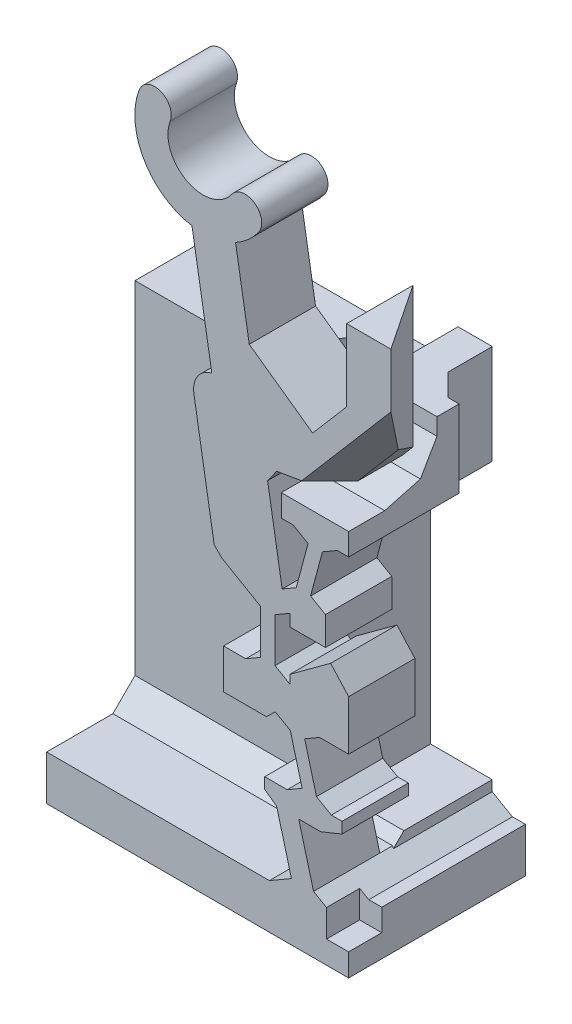
SolidWorks part; units mm, degrees
material "Nylon 6/12"
ref_plane "Front Plane" through (0, 0, 0) normal (0, 0, 1) x (1, 0, 0)
ref_plane "Top Plane" through (0, 0, 0) normal (0, 1, 0) x (1, 0, 0)
ref_plane "Right Plane" through (0, 0, 0) normal (1, 0, 0) x (0, 0, -1)
sketch "Sketch-SkeletonConfigUp" plane through (0, 0, 0) normal (0, 0, 1) x (1, 0, 0)
  line L0 (0, 0) -> (0, -50000) construction
  line L1 (0, 0) -> (4.5811, 6.2164) construction
  line L2 (9.8143, 13.3177) -> (4.5811, 13.945) construction
  line L3 (4.5811, 13.945) -> (2.9713, 10.4094) construction
  line L4 (2.9713, 10.4094) -> (4.5811, 6.2164) construction
  line L5 (4.5811, 13.945) -> (6.2429, 19.1409) construction
  line L6 (2.9713, 10.4094) -> (0.0405, 27.8193) construction
  line L7 (4.5811, 6.2164) -> (9.8143, 13.3177) construction
  line L8 (-587.3593, -797.0242) -> (9.8143, 13.3177) construction
  dimension "D2" = 7.7221
  dimension "D3" = 8.8212
  dimension "D4" = 5.2707
  dimension "D5" = 119.553
  dimension "D6" = 3.8848
  dimension "D7" = 5.4552
  dimension "D8" = 17.6549
  dimension "D9" = 4.4914
  dimension "D10" = 6.745
  dimension "D11" = 145.964
  dimension "D12" = 143.612
sketch "Sketch-SkeletonConfigDown" plane through (0, 0, 0) normal (0, 0, 1) x (1, 0, 0)
  line L0 (0, 0) -> (0, -50000) construction
  line L1 (0, 0) -> (4.5811, 6.2164) construction
  line L2 (9.8143, 13.3177) -> (4.5811, 13.945) construction
  line L3 (4.5811, 13.945) -> (6.1909, 10.4094) construction
  line L4 (6.1909, 10.4094) -> (4.5811, 6.2164) construction
  line L5 (4.5811, 13.945) -> (1.753, 18.6098) construction
  line L6 (6.1909, 10.4094) -> (-8.8652, 19.6294) construction
  line L7 (4.5811, 6.2164) -> (9.8143, 13.3177) construction
  line L8 (-589.9357, -800.5203) -> (9.8143, 13.3177) construction
  dimension "D2" = 7.7221
  dimension "D3" = 8.8212
  dimension "D4" = 5.2707
  dimension "D5" = 119.553
  dimension "D6" = 3.8848
  dimension "D7" = 5.4552
  dimension "D8" = 17.6549
  dimension "D9" = 4.4914
  dimension "D10" = 6.745
  dimension "D11" = 145.964
  dimension "D1" = 143.612
ref_plane "Plane-Cam Base" through (9.128, 0, 0) normal (1, 0, 0) x (0, 0, -1)
ref_plane "Plane-Down-to-Up Derailleur Clearance" through (6.628, 0, 0) normal (1, 0, 0) x (0, 0, -1)
ref_plane "Plane-Cam Cavity Roof" through (5.128, 0, 0) normal (1, 0, 0) x (0, 0, -1)
sketch "Sketch-SwitchBossUp" plane through (0, 0, 0) normal (0, 0, 1) x (1, 0, 0)
  line L0 (3.5811, 11.4759) -> (3.5811, 12.945) construction
  line L2 (6.5405, 21.1774) -> (6.5405, 24.4384)
  line L3 (6.5405, 24.4384) -> (8.5405, 24.4384)
  line L4 (8.5405, 24.4384) -> (8.5405, 20.4384)
  line L5 (5.5811, 12.5552) -> (5.5811, 11.263)
  line L7 (1.5115, 25.1048) -> (2.5464, 18.9575)
  line L8 (-0.4607, 24.7728) -> (0.4359, 19.4465)
  line L9 (2.9713, 10.4094) -> (0.0405, 27.8193) construction
  line L11 (-0.0396, 22.2712) -> (1.9326, 22.6032) construction
  line L15 (6.628, -55) -> (6.628, 55) construction
  line L16 (2.9713, 10.4094) -> (4.5811, 6.2164) construction
  line L17 (3.5811, 12.945) -> (3.5811, 14.945) construction
  line L18 (5.5811, 12.945) -> (5.5811, 14.945) construction
  line L19 (4.2561, 13.945) -> (4.9061, 13.945) construction
  line L20 (3.5811, 14.945) -> (5.5811, 14.945) construction
  line L21 (3.5811, 12.945) -> (5.5811, 12.945) construction
  line L22 (4.5811, 12.945) -> (4.5811, 14.945) construction
  line L23 (4.5811, 6.2164) -> (8.5405, 7.1023) construction
  line L24 (1.9713, 9.4094) -> (1.9713, 11.4094) construction
  line L25 (3.9713, 9.4094) -> (3.9713, 11.4094) construction
  line L26 (3.9713, 9.4094) -> (1.9713, 9.4094) construction
  line L27 (1.9713, 11.4094) -> (3.9713, 11.4094) construction
  line L28 (3.5811, 7.2164) -> (5.5811, 7.2164) construction
  line L29 (3.5811, 7.2164) -> (3.5811, 5.2164) construction
  line L30 (5.5811, 7.2164) -> (5.5811, 5.2164) construction
  line L31 (3.5811, 5.2164) -> (5.5811, 5.2164) construction
  line L32 (4.9061, 6.2164) -> (4.2561, 6.2164) construction
  line L40 (3.2963, 10.4094) -> (2.6463, 10.4094) construction
  line L43 (2.874, 4.5093) -> (0.7934, 4.5093) construction
  line L51 (4.9929, 19.3693) -> (2.5464, 18.9575)
  line L66 (0.0405, 27.8193) -> (0.0405, 50027.8193) construction
  line L74 (0.5455, 12.7717) -> (-0.3728, 18.2264)
  line L75 (0.3841, 13.7302) -> (2.3564, 14.0622) construction
  line L76 (5.5811, 11.263) -> (5.5811, 12.5552) construction
  line L80 (5.8152, 10.763) -> (6.628, 9.8603)
  line L81 (8.5405, 1033.6218) -> (8.5405, 20.4384) construction
  line L82 (2.5464, 18.9575) -> (3.5585, 12.945) construction
  line L83 (3.6203, 12.5779) -> (2.8784, 16.9852)
  line L84 (2.8784, 16.9852) -> (6.0405, 17.5175)
  line L85 (6.9307, 9.5241) -> (8.5405, 7.7363) construction
  line L88 (3.5811, 16.3347) -> (6.8573, 16.3347)
  line L92 (3.7762, 8.3129) -> (6.9307, 9.5241) construction
  line L93 (6.3311, 4.3289) -> (5.3706, 3.937)
  line L95 (2.5464, 18.9575) -> (2.8784, 16.9852) construction
  line L96 (2.7124, 17.9713) -> (8.5405, 18.9524) construction
  line L97 (2.7124, 17.9713) -> (1.7262, 17.8053) construction
  line L98 (1.9713, 9.0197) -> (0.9713, 9.0197)
  line L99 (0.9713, 9.0197) -> (0.9713, 7.2164)
  line L100 (0.9713, 7.2164) -> (2.9061, 7.2164)
  line L101 (4.5811, 6.2164) -> (6.9307, 9.5241) construction
  line L103 (0.0405, 27.8193) -> (1.9448, 26.4638) construction
  line L104 (6.9307, 9.5241) -> (8.5405, 7.7363) construction
  line L106 (13.4416, 14.945) -> (5.5811, 14.945) construction
  line L107 (1.9713, 9.4094) -> (1.9713, 9.0197) construction
  line L109 (0.0405, 27.8193) -> (-2.1498, 28.6358) construction
  line L110 (8.5405, 20.4384) -> (6.0405, 17.5175)
  line L111 (6.628, 9.8603) -> (6.628, 8.3653)
  line L112 (6.628, 9.8603) -> (6.9307, 9.5241) construction
  line L113 (2.8311, 4.8267) -> (2.8311, 4.3267)
  line L114 (7.3693, 7.7363) -> (7.3563, 7.7363) construction
  line L115 (6.8573, 16.3347) -> (13.4416, 16.3347)
  line L116 (13.4416, 16.3347) -> (13.4416, -1.1653)
  line L117 (13.4416, -1.1653) -> (5.0405, -1.1653)
  line L119 (10.4375, 14.0252) -> (10.4375, 2.1692)
  line L121 (5.0405, -1.1653) -> (5.0405, 1.437) construction
  line L122 (8.237, 12.8031) -> (10.8393, 12.8031) construction
  line L123 (10.8393, 12.8031) -> (13.4416, 12.8031) construction
  line L124 (10.4375, 2.1692) -> (9.128, 0.8597)
  line L125 (8.5405, 7.5847) -> (13.4416, 7.5847) construction
  line L127 (5.5811, 15.3347) -> (5.5811, 14.945) construction
  line L130 (6.0405, 0.8597) -> (9.128, 0.8597)
  line L132 (2.8311, 4.3267) -> (3.3706, 3.937)
  line L133 (2.9713, 10.4094) -> (6.1909, 10.4094) construction
  line L134 (4.5811, 10.4094) -> (4.5811, 13.945) construction
  line L135 (4.5811, 10.4094) -> (4.5811, 6.2164) construction
  line L136 (0.8973, 12.4192) -> (0.5455, 12.7717)
  line L137 (3.9713, 9.4094) -> (5.5811, 7.2164) construction
  line L139 (5.8152, 10.763) -> (3.9713, 9.4094)
  line L141 (4.0405, 1.437) -> (3.0405, 0.8597)
  line L142 (3.0405, 0.8597) -> (3.0405, -1.1653)
  line L143 (8.5405, 20.4384) -> (8.5405, 18.9524) construction
  line L145 (8.5405, 17.9384) -> (8.5405, -49992.0368) construction
  line L147 (5.5811, 11.263) -> (5.5811, 12.5552) construction
  line L149 (6.3311, 4.8289) -> (6.3311, 4.3289)
  line L150 (3.0405, -1.1653) -> (5.0405, -1.1653)
  line L151 (3.3706, 3.937) -> (5.3706, 3.937) construction
  line L152 (4.792, 14.945) -> (4.2561, 12.945)
  line L153 (5.442, 14.945) -> (4.9061, 12.945)
  line L157 (3.5811, 16.3347) -> (3.5811, 15.3347)
  line L158 (6.117, 15.3347) -> (9.128, 15.3347)
  line L162 (3.2963, 11.4094) -> (3.2963, 9.4094)
  line L164 (2.6463, 11.4094) -> (2.6463, 9.4094)
  line L169 (3.9882, 7.2164) -> (4.5241, 5.2164)
  line L170 (5.1741, 5.2164) -> (4.6382, 7.2164)
  line L176 (4.6382, 7.2164) -> (5.315, 7.6072)
  line L177 (5.5811, 7.2164) -> (5.5811, 7.6072) construction
  line L180 (3.5811, 5.2164) -> (3.5811, 4.8267) construction
  line L181 (3.5811, 4.8267) -> (2.8311, 4.8267)
  line L184 (5.5811, 5.2164) -> (5.5811, 4.8267) construction
  line L186 (9.128, -55) -> (9.128, 55) construction
  line L187 (2.6463, 9.4094) -> (1.9713, 9.0197)
  line L188 (3.2963, 9.4094) -> (3.9713, 9.0197)
  line L189 (3.2963, 11.4094) -> (3.9713, 11.7991)
  line L190 (2.6463, 11.4094) -> (0.8973, 12.4192)
  line L191 (3.9713, 11.4094) -> (3.9713, 11.7991) construction
  line L192 (3.9713, 11.7991) -> (3.9713, 11.263)
  line L193 (4.9061, 12.945) -> (5.5811, 12.5552)
  line L194 (4.2561, 12.945) -> (3.6203, 12.5779)
  line L195 (3.9713, 11.263) -> (5.5811, 11.263)
  line L196 (3.9713, 9.4094) -> (3.9713, 9.0197)
  line L197 (3.5811, 7.2164) -> (3.5811, 7.6072) construction
  line L200 (5.8453, 4.8289) -> (6.3311, 4.8289)
  line L201 (2.8311, 4.3267) -> (2.8311, 3.937) construction
  line L202 (2.8311, 3.937) -> (3.3706, 3.937) construction
  line L203 (10.4375, 14.0252) -> (9.128, 15.3347)
  line L204 (5.0405, 1.437) -> (3.0405, 1.437) construction
  line L205 (3.0405, 1.437) -> (3.0405, 0.8597) construction
  line L206 (5.0405, 1.437) -> (6.0405, 0.8597)
  line L207 (8.5405, 18.9524) -> (8.5405, 17.9384) construction
  line L208 (6.0405, 17.5175) -> (8.5405, 17.9384) construction
  line L209 (8.5405, 20.4384) -> (8.5405, 17.9384) construction
  line L210 (6.5405, 21.1774) -> (4.9929, 19.3693)
  line L211 (5.0405, 1.437) -> (4.3706, 3.937)
  line L212 (4.0405, 1.437) -> (3.3706, 3.937)
  line L213 (5.3706, 3.937) -> (4.3706, 3.937)
  line L214 (4.792, 14.945) -> (4.1169, 15.3347)
  line L215 (4.1169, 15.3347) -> (3.5811, 15.3347)
  line L216 (5.442, 14.945) -> (6.117, 15.3347)
  line L217 (5.5811, 12.945) -> (5.5811, 12.5552) construction
  line L218 (5.442, 14.945) -> (5.442, 15.3347) construction
  line L219 (6.117, 15.3347) -> (4.1169, 15.3347) construction
  line L220 (3.5811, 4.8267) -> (5.5811, 4.8267) construction
  line L221 (4.5241, 5.2164) -> (3.8491, 4.8267)
  line L222 (3.8491, 4.8267) -> (3.5811, 4.8267)
  line L223 (5.1741, 5.2164) -> (5.8453, 4.8289)
  line L224 (3.5811, 7.6072) -> (5.5811, 7.6072) construction
  line L225 (3.9882, 7.2164) -> (3.3114, 7.6072)
  line L226 (5.315, 7.6072) -> (6.628, 7.6072)
  line L227 (6.628, 7.6072) -> (6.628, 8.3653)
  line L228 (3.5811, 7.6072) -> (0.9713, 7.6072) construction
  line L229 (3.3114, 7.6072) -> (2.9061, 7.2164)
  arc A0 (1.5115, 25.1048) -> (2.5558, 26.0289) centre (0.0405, 27.8193) ccw
  arc A1 (-0.4607, 24.7728) -> (-2.8525, 28.8978) centre (0.0405, 27.8193) cw
  arc A2 (-2.8525, 28.8978) -> (-1.447, 28.3738) centre (-2.1498, 28.6358) cw
  arc A3 (2.5558, 26.0289) -> (1.3338, 26.8987) centre (1.9448, 26.4638) ccw
  arc A4 (-1.447, 28.3738) -> (1.3338, 26.8987) centre (0.0405, 27.8193) ccw
  arc A5 (3.5811, 12.945) -> (3.5811, 14.945) centre (3.1778, 13.945) ccw construction
  arc A6 (5.5811, 12.945) -> (5.5811, 14.945) centre (5.9843, 13.945) cw construction
  arc A7 (2.5293, 9.921) -> (1.9713, 11.4094) centre (1.568, 10.4094) ccw construction
  arc A8 (3.9713, 11.4094) -> (3.9713, 9.4094) centre (4.3745, 10.4094) ccw construction
  arc A9 (3.5811, 7.2164) -> (3.5811, 5.2164) centre (3.1779, 6.2164) cw construction
  arc A10 (5.5811, 7.2164) -> (5.5811, 5.2164) centre (5.9844, 6.2164) ccw construction
  arc A19 (-0.3728, 18.2264) -> (0.4359, 19.4465) centre (0.6836, 18.4042) cw
  circle A28 centre (0.0405, 27.8193) radius 2.3375 construction
  arc A29 (1.9713, 9.4094) -> (2.5293, 9.921) centre (1.568, 10.4094) ccw construction
  point P53 (4.5811, 13.945)
  point P63 (2.9713, 10.4094)
  point P93 (0.9465, 22.4372)
  dimension "D23" = 1.5875
  dimension "D24" = 0.75
  dimension "D2" = 2
  dimension "D5" = 2
  dimension "D6" = 0.65
  dimension "D8" = 42
  dimension "D7" = 2
  dimension "D11" = 8.5
  dimension "D14" = 7.5
  dimension "D4" = 3
  dimension "D16" = 42
  dimension "D31" = 120
  dimension "D32" = 120
  dimension "D33" = 120
  dimension "D34" = 120
  dimension "D17" = 0.5
  dimension "D20" = 3.5
  dimension "D21" = 1
  dimension "D18" = 45
  dimension "D9" = 17.5
  dimension "D22" = 1
  dimension "D15" = 45
  dimension "D38" = 2
  dimension "D39" = 0.5
  dimension "D41" = 1
  dimension "D42" = 45
  dimension "D43" = 120
  dimension "D44" = 2
  dimension "D45" = 2.5
  dimension "D46" = 2.5
  dimension "D47" = 4
  dimension "D48" = 2
  dimension "D10" = 15
  dimension "D12" = 2.5
  dimension "D13" = 1
  dimension "D19" = 1
  dimension "D25" = 15
  dimension "D26" = 120
  dimension "D35" = 120
  dimension "D27" = 15
  dimension "D28" = 30
  dimension "D29" = 30
  dimension "D30" = 30
  dimension "D36" = 30
extrude "Boss-Switch Body" add sketch "Sketch-SwitchBossUp" along normal blind 3
sketch "Sketch1" plane through (0, 0, 0) normal (0, 0, -1) x (-1, 0, 0)
  line L1 (-7.5811, -1.1653) -> (0.4122, -1.1653)
  line L2 (-7.5811, -1.1653) -> (-7.5811, 0.8597)
  line L4 (0.4122, -1.1653) -> (0.4122, 0.8597)
  line L5 (-3.5811, 18.8347) -> (-7.5811, 18.8347)
  line L10 (-7.5811, 18.8347) -> (-7.5811, 15.3347)
  line L11 (-4.0405, 1.437) -> (-5.0405, 1.437)
  line L12 (-7.5811, 15.3347) -> (-3.5811, 15.3347)
  line L13 (-4.0405, 1.437) -> (-3.0405, 0.8597)
  line L14 (-3.5811, 15.3347) -> (-3.5811, 18.8347)
  line L20 (-4.3706, 3.937) -> (-5.0405, 1.437) construction
  line L22 (-3.0405, -1.1653) -> (-13.4416, -1.1653) construction
  line L23 (-3.0405, 0.8597) -> (0.4122, 0.8597)
  line L24 (-5.0405, 1.437) -> (-6.0405, 0.8597)
  line L25 (-6.0405, 0.8597) -> (-7.5811, 0.8597)
  line L27 (-3.5811, 16.3347) -> (-3.5811, 15.3347) construction
  point P5 (-3.5811, 15.3347)
  dimension "D1" = 3.5
  dimension "D4" = 4
extrude "Boss-Flange Width" add sketch "Sketch1" along normal blind 5
ref_plane "Plane-Sta2Sit Groove" through (0.0405, 0, 0) normal (1, 0, 0) x (0, 0, -1)
ref_plane "Plane-Cam Outer Surface" through (-12.0395, 0, 0) normal (1, 0, 0) x (0, 0, -1)
ref_plane "Plane-FlangeTop" through (-7.0395, 0, 0) normal (1, 0, 0) x (0, 0, -1)
sketch "Sketch2" plane through (-7.0395, 0, 0) normal (1, 0, 0) x (0, 0, -1)
  line L0 (5, 15.3347) -> (-3, 15.3347) construction
  line L1 (5, 17.3347) -> (1, 17.3347)
  line L2 (5, 17.3347) -> (5, 15.3347)
  line L3 (5, 15.3347) -> (1, 15.3347)
  line L4 (1, 17.3347) -> (1, 15.3347)
  line L10 (-3, -1.1653) -> (-3, 16.3347) construction
  line L11 (5, 0.8597) -> (-3, 0.8597)
  line L12 (5, 0.8597) -> (5, -1.1653)
  line L13 (5, -1.1653) -> (-3, -1.1653)
  line L14 (-3, 0.8597) -> (-3, -1.1653)
  line L15 (0, 10.4094) -> (0, 27.8193) construction
  line L17 (5, 0.8597) -> (5, -1.1653) construction
  line L18 (-3, 0.8597) -> (0, 0.8597) construction
  dimension "D1" = 1
  dimension "D2" = 2
extrude "Boss-Flange Height" add sketch "Sketch2" along normal up to surface (11.6675 mm away)
sketch "Sketch10" plane through (0, 15.3347, 0) normal (0, 1, 0) x (1, 0, 0)
  line L0 (9.128, -55) -> (9.128, 55) construction
  line L1 (7.5811, 5) -> (5.128, 5)
  line L2 (7.5811, 5) -> (7.5811, 2)
  line L3 (7.5811, 2) -> (5.128, 2)
  line L5 (4.628, 7) -> (4.628, 1) construction
  line L6 (3.5811, 1) -> (-7.0395, 1) construction
  line L8 (5.128, 5) -> (5.128, 2)
  dimension "D1" = 1
  dimension "D2" = 0.5
  dimension "D3" = 4.5
extrude "Cut-Up-To-Down Derailleur Clearance" cut sketch "Sketch10" along normal up to next
sketch "Sketch17" plane through (0, 15.3347, 0) normal (0, -1, 0) x (1, 0, 0)
  line L0 (5.128, -5) -> (-7.0395, -5)
  line L1 (5.128, -5) -> (-7.0395, -5) construction
  line L2 (-7.0395, -5) -> (-7.0395, -1)
  line L3 (-7.0395, -1) -> (5.128, -1)
  line L4 (5.128, -1) -> (5.128, -5)
  line L5 (-7.0395, -1) -> (-7.0395, -5) construction
extrude "Boss-Flange Support" add sketch "Sketch17" along normal up to surface (14.475 mm away) up to face at (-1.9995, 0.8597, -1)
sketch "Sketch-HolePositions" plane through (0, -1.1653, 0) normal (0, -1, 0) x (1, 0, 0)
  line L0 (-7.0395, -3) -> (7.5811, -3) construction
  line L1 (7.5811, -5) -> (-7.0395, -5) construction
  line L2 (7.5811, -5) -> (7.5811, 0) construction
  line L4 (-7.0395, -22.2167) -> (-7.0395, 22.2167) construction
  line L5 (3.5811, -1) -> (3.5811, -5) construction
  point P6 (-4.0395, -3)
  point P7 (0.5811, -3)
  dimension "D1" = 3
  dimension "D2" = 3
  dimension "D3" = 2
sketch "Sketch6" plane through (0, -1.1653, 0) normal (0, -1, 0) x (-1, 0, 0)
  point P0 (4.0395, 3)
  point P3 (-0.5811, 3)
hole_wizard "Tap Drill for M2x0.4 Tap1" positions "Sketch6" profile "Sketch5" hole size "M2x0.4" standard "ANSI Metric" end condition through all
sketch "Sketch5" plane through (-4.0395, -1.1653, -3) normal (1, 0, 0) x (0, 0, -1)
  line L0 (0, 0) -> (0, 30.5511)
  line L1 (0, 30.5511) -> (0.8, 30.5511)
  line L2 (0.8, 30.5511) -> (0.8, 0)
  line L5 (0.8, 0) -> (0, 0)
  line L11 (0, -6.35) -> (0, 107.95) construction
  dimension "Thru Hole Dia." = 1.6
  dimension "Thru Hole Depth" = 30.5511
sketch "Sketch9" plane through (0, -1.1653, 0) normal (0, -1, 0) x (1, 0, 0)
  point P0 (-4.0395, -3)
  point P3 (0.5811, -3)
hole_wizard "M2 Clearance Hole2" positions "Sketch9" profile "Sketch8" hole size "M2" standard "ANSI Metric"
sketch "Sketch8" plane through (-4.0395, -1.1653, -3) normal (1, 0, 0) x (0, 0, -1)
  line L0 (0, 0) -> (0, 15.721)
  line L1 (0, 15.721) -> (1.2, 15)
  line L2 (1.2, 15) -> (1.2, 0)
  line L5 (1.2, 0) -> (0, 0)
  line L10 (0, 15.721) -> (-1.2, 15) construction
  line L11 (0, -6.35) -> (0, 107.95) construction
  dimension "Hole Dia." = 2.4
  dimension "Hole Depth" = 15
  dimension "Drill Angle" = 118
sketch "Sketch-Measurements for Derailleur Ramps" plane through (0, 0, 0) normal (0, 0, 1) x (1, 0, 0)
  line L0 (2.8784, 16.9852) -> (2.5464, 18.9575)
  line L1 (2.7124, 17.9713) -> (1.7262, 17.8053)
  line L2 (2.9713, 10.4094) -> (0.0405, 27.8193) construction
  line L3 (1.7262, 17.8053) -> (-1.8937, 15.3603)
  line L4 (6.1909, 10.4094) -> (-8.8652, 19.6294) construction
  line L5 (1.7262, 17.8053) -> (2.6012, 12.6077)
  line L6 (2.6012, 12.6077) -> (-1.8937, 15.3603)
  line L7 (-0.0837, 16.5828) -> (-0.0837, 17.8053)
  line L8 (-0.0837, 17.8053) -> (1.7262, 17.8053)
  line L9 (6.1909, 10.4094) -> (2.9713, 10.4094)
  line L10 (5.386, 8.3129) -> (3.7762, 8.3129)
  line L12 (6.1909, 10.4094) -> (4.5811, 6.2164) construction
  line L13 (4.5811, 8.3129) -> (4.5811, 8.7912)
  line L14 (4.5811, 6.2164) -> (5.386, 8.3129)
  line L15 (2.9713, 10.4094) -> (4.5811, 6.2164) construction
  line L16 (3.7762, 8.3129) -> (4.5811, 6.2164)
  line L17 (5.386, 8.3129) -> (5.386, 8.7912)
  dimension "D1" = 1.81
  dimension "D2" = 0.8049
sketch "Sketch12" plane through (0, 24.4384, 0) normal (0, 1, 0) x (1, 0, 0)
  line L0 (6.5405, 0) -> (8.5405, -3)
  line L1 (8.5405, -3) -> (8.5405, 0)
  line L2 (8.5405, 0) -> (6.5405, 0)
extrude "Cut-Up-to-Down Cantilever Slope" cut sketch "Sketch12" against normal up to next
ref_plane "Plane1" through (0, 7.1023, 0) normal (0, 1, 0) x (1, 0, 0)
sketch "Sketch-Derailleur Location" plane through (0, 7.1023, 0) normal (0, 1, 0) x (1, 0, 0)
  line L0 (8.5405, 0) -> (8.5405, -3)
  line L1 (4.0405, -3) -> (3.0405, -3) construction
  line L2 (-119237.4187, 0) -> (9.8143, 0) construction
  point P0 (8.5405, 0)
  point P8 (8.5405, -1.5)
ref_plane "Plane-Cantilever Cut" [suppressed] through (7.0848, 8.5204, -1.9058) normal (-0.6301, -0.7578, 0.1695) x (-0.7765, 0.6151, -0.1368)
sketch "Sketch14" [suppressed] plane through (7.0848, 8.5204, -1.9058) normal (-0.6301, -0.7578, 0.1695) x (-0.7765, 0.6151, -0.1368)
  line L0 (2.3023, -1.6911) -> (-0.3551, -1.6911)
  line L2 (2.3023, -4.3362) -> (2.3023, -1.6911)
  line L3 (-0.3551, -1.6911) -> (-0.3551, -4.4608)
  line L5 (-0.3551, -4.4608) -> (1.0087, -5.0843)
  line L6 (1.0087, -5.0843) -> (2.3023, -4.3362)
extrude "Cut-Down-to-Up Cantilever Slope" [suppressed] cut sketch "Sketch14" against normal up to next
sketch "Sketch16" plane through (0, 0, 0) normal (0, 0, -1) x (-1, 0, 0)
  line L0 (-7.5811, 18.8347) -> (-13.4416, 18.8347)
  line L1 (-13.4416, 18.8347) -> (-13.4416, -1.1653)
  line L2 (-13.4416, -1.1653) -> (-6.628, -1.1653)
  line L3 (-13.4416, -1.1653) -> (-5.0405, -1.1653) construction
  line L4 (-6.628, -1.1653) -> (-6.628, 5.2038)
  line L5 (-6.628, 5.2038) -> (-8.0037, 5.2038)
  line L6 (-8.0037, 5.2038) -> (-8.0037, 12.0484)
  line L7 (-8.0037, 12.0484) -> (-6.628, 12.0484)
  line L8 (-6.628, 12.0484) -> (-6.628, 17.9477)
  line L9 (-6.628, 55) -> (-6.628, -55) construction
  line L10 (-3.5811, 18.8347) -> (-6.5405, 18.8347) construction
  line L11 (-7.5811, 18.8347) -> (-6.628, 17.9477)
extrude "Cut-Down-to-Up Derailleur Clearance" cut sketch "Sketch16" against normal through all and the other way through all
ref_plane "Plane-Symmetry Plane" through (0, 0, 1.5) normal (0, 0, 1) x (1, 0, 0)
sketch "Sketch-Cable Center Point" plane through (0, 0, 1.5) normal (0, 0, 1) x (1, 0, 0)
  line L0 (0.0405, 27.8193) -> (0.1722, 27.0366)
  line L1 (2.9713, 10.4094) -> (0.0405, 27.8193) construction
  point P0 (0.0405, 27.8193)
  dimension "D1" = 0.7937
chamfer "Chamfer-Flange Support" distance 1.5 angle 45 1 edges at (3.5811, 17.3347, -3)
chamfer "Chamfer-Flange Support 2" distance 1 angle 45 2 edges at (5.128, 17.0847, -2) (5.128, 15.3347, -1.5)
chamfer "Chamfer-Flange Support 3" distance 1 angle 45 1 edges at (-1.9995, 0.8597, -1)
sketch "Sketch18" plane through (6.628, 0, 0) normal (1, 0, 0) x (0, 0, -1)
  line L1 (-3, -0.1403) -> (-1.5, -0.1403)
  line L2 (-3, -0.1403) -> (-3, 1.437)
  line L3 (-3, 1.437) -> (-1.5, 1.437)
  line L4 (-1.5, -0.1403) -> (-1.5, 1.437)
  line L5 (0.5774, 1.437) -> (0, 1.437) construction
  line L6 (-3, -1.1653) -> (-3, 0.8597) construction
  line L7 (-3, 0.8597) -> (5, 0.8597) construction
  dimension "D1" = 1.5
  dimension "D2" = 1
extrude "Cut-Down-to-Up Derailleur Clearance 2" cut sketch "Sketch18" against normal blind 1
sketch "Sketch19" plane through (0, 0, 0) normal (0, 0, 1) x (1, 0, 0)
  line L7 (3.5811, 18.8983) -> (6.628, 18.8983)
  line L8 (6.628, 18.8983) -> (6.628, 16.3347)
  line L9 (6.628, 16.3347) -> (3.5811, 16.3347)
  line L10 (3.5811, 16.3347) -> (3.5811, 18.8983)
  line L11 (6.628, 16.3347) -> (6.628, 17.9477) construction
  point P4 (6.628, 18.8983)
extrude "Cut-Up-to-Down Cantilever Clearance" cut sketch "Sketch19" against normal up to surface (1 mm away) up to face at (1.4435, 12.7784, -1)
chamfer "Chamfer1" distance 1 angle 60 1 edges at (5.1045, 16.3347, -1) first distance on face at (5.1045, 16.3347, 1)
chamfer "Chamfer3" distance 0.75 angle 60 1 edges at (3.5811, 16.7007, -1) first distance on face at (3.5811, 16.2811, 0.8)
chamfer "Chamfer4" distance 0.5 angle 60 1 edges at (4.205, 15.3347, -1) first distance on face at (5.0385, 15.3347, 0.5227)
chamfer "Chamfer5" distance 0.5 angle 45 1 edges at (2.8784, 16.9852, 1.5)
chamfer "Chamfer6" distance 2.5 angle 45 1 edges at (2.5464, 18.9575, 1.5)
chamfer "Chamfer7" distance 1 angle 45 1 edges at (7.2905, 18.978, 3)
sketch "Sketch22" plane through (0, 0, 0) normal (0, 0, 1) x (1, 0, 0)
  line L0 (6.628, 17.9477) -> (7.5811, 18.8347) construction
  line L1 (6.628, 18.8347) -> (7.5811, 18.8347) construction
  line L2 (6.628, 17.9477) -> (6.628, 18.8347) construction
  line L3 (6.628, 17.9477) -> (7.5811, 18.8347)
  line L4 (6.628, 18.8347) -> (7.5811, 18.8347)
  line L5 (6.628, 17.9477) -> (6.628, 18.8347)
extrude "Cut-Extrude3" cut sketch "Sketch22" against normal up to next
chamfer "Chamfer8" distance 0.5 angle 45 1 edges at (5.1045, 16.3347, 0) first distance on face at (4.2965, 17.2286, -0.5161)
sketch "Sketch23" plane through (0, 0, -1) normal (0, 0, 1) x (1, 0, 0)
  line L0 (5.128, 1.8597) -> (2.3369, 1.8597)
  line L1 (-7.0395, 1.8597) -> (5.128, 1.8597) construction
  line L2 (2.3369, 1.8597) -> (2.3369, 14.3347)
  line L3 (2.3369, 14.3347) -> (5.128, 14.3347)
  line L4 (5.128, 14.3347) -> (5.128, 1.8597)
extrude "Cut-Extrude4" cut sketch "Sketch23" against normal through all
equation "\"axle-diameter\"=2"
equation "\"switch-thickness\"=12"
equation "\"base-width\"=4.0"
equation "\"axle-bushing-radius\"=3"
equation "\"clearance\"= 0.25"
equation "\"arm-width\"=1.5"
equation "\"min-diameter\"=70"
equation "\"alpha\"=143.6120"
equation "\"gamma\"=119.5526"
equation "\"delta\"=145.9637"
equation "\"epsilon\"=6.7452"
equation "\"l_AB\"=8.8212"
equation "\"l_AC\"=4.4914"
equation "\"l_BD\"=5.2707"
equation "\"l_CD\"=3.8848"
equation "\"l_CE\"=17.6549"
equation "\"l_DF\"=5.4552"
equation "\"l_OA\"=7.7221"
equation "\"D2@Sketch-SkeletonConfigUp\" = \"l_OA\""
equation "\"D3@Sketch-SkeletonConfigUp\" = \"l_AB\""
equation "\"D4@Sketch-SkeletonConfigUp\" = \"l_BD\""
equation "\"D5@Sketch-SkeletonConfigUp\" = \"gamma\""
equation "\"D6@Sketch-SkeletonConfigUp\" = \"l_CD\""
equation "\"D7@Sketch-SkeletonConfigUp\" = \"l_DF\""
equation "\"D8@Sketch-SkeletonConfigUp\" = \"l_CE\""
equation "\"D9@Sketch-SkeletonConfigUp\" = \"l_AC\""
equation "\"D_groove\"=3.175"
equation "\"D7@Sketch-SkeletonConfigDown\" = \"l_DF\""
equation "\"D6@Sketch-SkeletonConfigDown\" = \"l_CD\""
equation "\"D2@Sketch-SkeletonConfigDown\" = \"l_OA\""
equation "\"D3@Sketch-SkeletonConfigDown\" = \"l_AB\""
equation "\"D9@Sketch-SkeletonConfigDown\" = \"l_AC\""
equation "\"D8@Sketch-SkeletonConfigDown\" = \"l_CE\""
equation "\"D5@Sketch-SkeletonConfigDown\" = \"gamma\""
equation "\"D4@Sketch-SkeletonConfigDown\" = \"l_BD\""
equation "\"D1@Sketch-SkeletonConfigDown\" = \"alpha\""
equation "\"hinge_length\"=1.5"
equation "\"hinge_depth\"=0.25"
equation "\"D10@Sketch-SkeletonConfigUp\"=\"epsilon\""
equation "\"D11@Sketch-SkeletonConfigUp\"=\"delta\""
equation "\"D12@Sketch-SkeletonConfigUp\"=\"alpha\""
equation "\"D11@Sketch-SkeletonConfigDown\"=\"delta\""
equation "\"D10@Sketch-SkeletonConfigDown\"=\"epsilon\""
equation "\"EE_dx\"=8.9056"
equation "\"EE_dy\"=8.1898"
equation "\"r_groove\"=\"D_groove\"/2"
equation "\"t_wall\"=25.4/16"
equation "\"width_lower\"=\"D_groove\"+\"t_wall\""
equation "\"cable_to_bottom\"=30.6257"
equation "\"switch_EE-up_base_dy\"=24"
equation "\"switch_EE-down_base_dy\"=16"
equation "\"D_axle\"=25.4/8"
equation "\"D_up_to_down\"=16"
equation "\"D_down_to_up\"=25"
equation "\"t_cam_base\"=7.5"
equation "\"D23@Sketch-SwitchBossUp\"=\"D_groove\"/2"
equation "\"D1@Sketch-Cable Center Point\"=\"D_groove\"/4"
